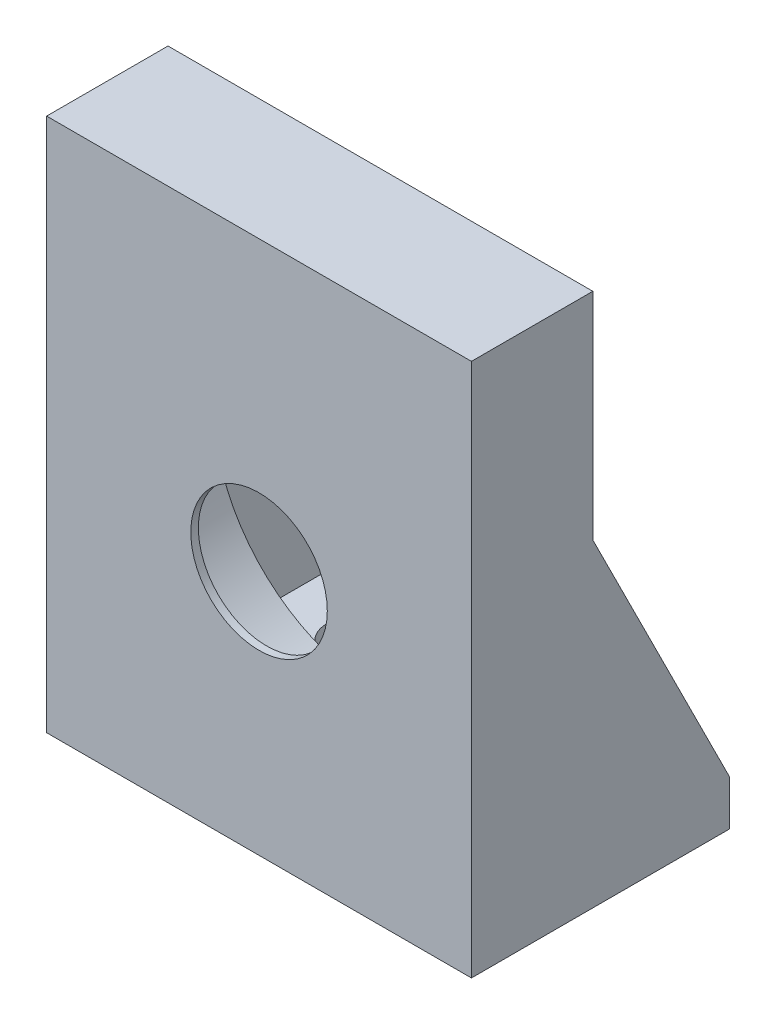
SolidWorks part; units mm, degrees
material "ABS"
ref_plane "Front Plane" through (0, 0, 0) normal (0, 0, 1) x (1, 0, 0)
ref_plane "Top Plane" through (0, 0, 0) normal (0, 1, 0) x (1, 0, 0)
ref_plane "Right Plane" through (0, 0, 0) normal (1, 0, 0) x (0, 0, -1)
sketch "Sketch2" plane through (0, 0, -2.5384) normal (0, 0, 1) x (1, 0, 0)
  line L1 (-92.7321, 37.036) -> (-64.7321, 37.036)
  line L2 (-92.7321, 37.036) -> (-92.7321, 1.836)
  line L3 (-92.7321, 1.836) -> (-64.7321, 1.836)
  line L4 (-64.7321, 37.036) -> (-64.7321, 1.836)
  line L5 (-92.7321, 37.036) -> (-64.7321, 1.836) construction
  line L6 (-92.7321, 1.836) -> (-64.7321, 37.036) construction
  line L8 (271.6524, 1.836) -> (-80.3476, 1.836) construction
  line L9 (-78.7321, 37.036) -> (-78.7321, 1.836) construction
  circle A0 centre (-78.7321, 18.036) radius 11
  circle A1 centre (-78.7321, 18.036) radius 4.5
  point P11 (-78.7321, 19.436)
  circle M1 centre (-78.7321, 23.036) radius 9.65
  circle M2 centre (-78.7321, 23.036) radius 10.7
  dimension "D1" = 22
  dimension "D2" = 9
  dimension "D3" = 19
  dimension "D4" = 14
  dimension "D5" = 35.2
  dimension "D6" = 28
extrude "Boss-Extrude3" add sketch "Sketch2" against normal blind 8 separate body contours L4 L1 L2 L3 A0 | A0 M1 | A0 M2 M1 region at (-78.7321, 36.5862, -2.5384) region at (-68.3545, 22.3746, -2.5384) region at (-78.7321, 29.3231, -2.5384)
sketch "Sketch3" plane through (-92.7321, 0, 0) normal (-1, 0, 0) x (0, 0, 1)
  line L0 (-9.5384, 1.836) -> (-19.5384, 1.836)
  line L1 (-19.5384, 1.836) -> (-19.5384, 4.836)
  line L2 (-19.5384, 4.836) -> (-9.5384, 24.836)
  line L5 (-19.5384, 4.836) -> (-9.5384, 4.836)
  line L6 (-9.5384, 4.836) -> (-9.5384, 1.836)
  line L7 (-9.5384, 24.836) -> (-9.5384, 4.836)
  dimension "D1" = 3
  dimension "D2" = 20
  dimension "D3" = 10
extrude "Boss-Extrude4" add sketch "Sketch3" against normal up to surface (28 mm away) contours L5 L1 L0 region at (-92.7321, 3.336, -14.5384) up to face at (-64.7321, 19.436, -6.5384)
extrude "Boss-Extrude5" add sketch "Sketch3<3>" against normal blind 3 contours L2 L5 region at (-92.7321, 11.5026, -12.8718)
sketch "Sketch3<3>" plane through (-92.7321, 0, 0) normal (-1, 0, 0) x (0, 0, 1) same geometry as "Sketch3"
extrude "Boss-Extrude6" add sketch "Sketch3<4>" along normal blind 3 from surface contours L2 L5 region at (-92.7321, 11.5026, -12.8718) starting at face at (-64.7321, 14.5693, -10.8718)
sketch "Sketch3<4>" plane through (-92.7321, 0, 0) normal (-1, 0, 0) x (0, 0, 1) same geometry as "Sketch3"
sketch "Sketch4" plane through (0, 4.836, 0) normal (0, 1, 0) x (1, 0, 0)
  line L0 (-67.7321, 15.0384) -> (-89.7321, 15.0384) construction
  line L1 (-67.7321, 19.5384) -> (-67.7321, 10.5384) construction
  line L2 (-89.7321, 19.5384) -> (-89.7321, 10.5384) construction
  line L3 (-78.7321, 9.5384) -> (-78.7321, 19.5384) construction
  line L5 (-67.7321, 19.5384) -> (-89.7321, 19.5384) construction
  line L6 (-67.7321, 15.0384) -> (-78.7321, 15.0384) construction
  line L7 (-78.7321, 15.0384) -> (-89.7321, 15.0384) construction
  circle A0 centre (-72.7321, 15.0384) radius 2
  circle A1 centre (-72.7321, 15.0384) radius 3.5 construction
  circle A2 centre (-84.7321, 15.0384) radius 3.5 construction
  circle A3 centre (-84.7321, 15.0384) radius 2
  dimension "D1" = 4
  dimension "D2" = 7
  dimension "D3" = 6
extrude "Cut-Extrude1" cut sketch "Sketch4" against normal through all
extrude "Boss-Extrude7" add sketch "Sketch2<3>" against normal blind 0.5 contours A0 M2 | A0 A1 M1 | A0 M2 M1 region at (-78.7321, 12.0818, -2.5384) region at (-78.7321, 12.5737, -2.5384) region at (-78.7321, 22.5927, -2.5384)
sketch "Sketch2<3>" plane through (0, 0, -2.5384) normal (0, 0, 1) x (1, 0, 0) same geometry as "Sketch2"
